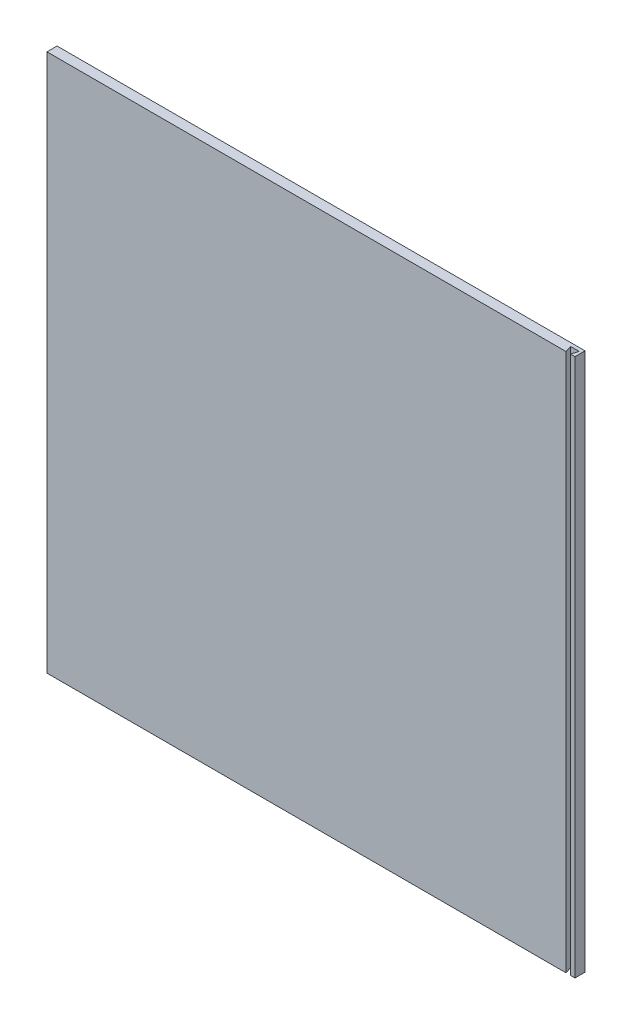
SolidWorks part; units mm, degrees
ref_plane "Front Plane" through (0, 0, 0) normal (0, 0, 1) x (1, 0, 0)
ref_plane "Top Plane" through (0, 0, 0) normal (0, 1, 0) x (1, 0, 0)
ref_plane "Right Plane" through (0, 0, 0) normal (1, 0, 0) x (0, 0, -1)
sketch "Sketch1" plane through (0, 0, 0) normal (0, 0, 1) x (1, 0, 0)
  line L1 (0, 0) -> (78.5, 0)
  line L2 (0, 0) -> (0, 80)
  line L3 (0, 80) -> (78.5, 80)
  line L4 (78.5, 0) -> (78.5, 80)
  dimension "D1" = 80
  dimension "D2" = 78.5
extrude "Boss-Extrude1" add sketch "Sketch1" along normal blind 1.5
sketch "Sketch2" plane through (0, 80, 0) normal (0, 1, 0) x (1, 0, 0)
  line L7 (78.5, -0.75) -> (73.8511, -0.75) construction
  line L8 (78.5, -1.5) -> (78.5, 0) construction
  line L13 (76.85, -0.5) -> (78.15, -0.5)
  line L14 (76.85, -0.5) -> (77.175, -1.5)
  line L15 (77.825, -1.5) -> (77.175, -1.5)
  line L16 (78.15, -0.5) -> (77.825, -1.5)
extrude "Cut-Extrude1" cut sketch "Sketch2" against normal up to surface (80 mm away) up to face at (39.25, 0, 0.75)
